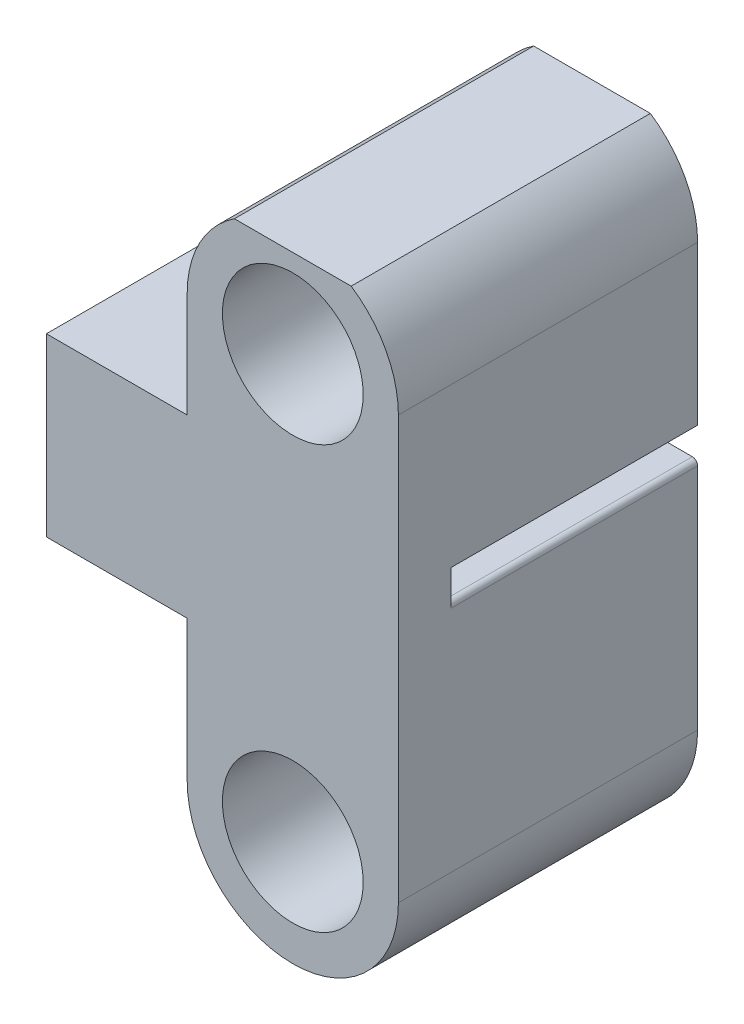
SolidWorks part; units mm, degrees
ref_plane "Front Plane" through (0, 0, 0) normal (0, 0, 1) x (1, 0, 0)
ref_plane "Top Plane" through (0, 0, 0) normal (0, 1, 0) x (1, 0, 0)
ref_plane "Right Plane" through (0, 0, 0) normal (1, 0, 0) x (0, 0, -1)
sketch "Sketch1" plane through (0, 0, 0) normal (0, 0, 1) x (1, 0, 0)
  line L0 (0, 0) -> (0, -12) construction
  line L1 (-3, 0) -> (-3, -12)
  line L2 (3, 0) -> (3, -12)
  arc A0 (3, 0) -> (-3, 0) centre (0, 0) ccw
  arc A1 (-3, -12) -> (3, -12) centre (0, -12) ccw
  circle A2 centre (0, 0) radius 2
  circle A3 centre (0, -12) radius 2
  dimension "D2" = 6
  dimension "D6" = 4
  dimension "D7" = 4
  dimension "D1" = 12
extrude "Boss-Extrude1" add sketch "Sketch1" along normal blind 8.5
sketch "Sketch2" plane through (3, 0, 0) normal (1, 0, 0) x (0, 0, -1)
  line L0 (-8.5, -6) -> (0, -6) construction
  line L1 (-8.5, -12) -> (-8.5, 0) construction
  line L2 (0, -12) -> (0, 0) construction
  line L3 (-4.25, 0) -> (-4.25, -12) construction
  line L4 (-8.5, 0) -> (0, 0) construction
  line L5 (-8.5, -12) -> (0, -12) construction
  circle A0 centre (-4.25, -8.5) radius 2
  dimension "D1" = 4
  dimension "D2" = 2.5
extrude "Cut-Extrude1" [suppressed] cut sketch "Sketch2" against normal through all
sketch "Sketch3" [suppressed] plane through (3, 0, 0) normal (1, 0, 0) x (0, 0, -1)
  line L1 (-0.6416, -8.5) -> (-2.4458, -5.375)
  line L2 (-2.4458, -5.375) -> (-6.0542, -5.375)
  line L3 (-6.0542, -5.375) -> (-7.8584, -8.5)
  line L4 (-7.8584, -8.5) -> (-6.0542, -11.625)
  line L5 (-6.0542, -11.625) -> (-2.4458, -11.625)
  line L6 (-2.4458, -11.625) -> (-0.6416, -8.5)
  line L7 (-1.8684, -4.375) -> (-6.6316, -4.375)
  line L8 (-6.6316, -4.375) -> (-9.0131, -8.5)
  line L9 (-9.0131, -8.5) -> (-6.6316, -12.625)
  line L10 (-6.6316, -12.625) -> (-1.8684, -12.625)
  line L11 (-1.8684, -12.625) -> (0.5131, -8.5)
  line L12 (0.5131, -8.5) -> (-1.8684, -4.375)
  circle A0 centre (-4.25, -8.5) radius 3.125 construction
  circle A1 centre (-4.25, -8.5) radius 4.125 construction
  dimension "D1" = 6.25
  dimension "D2" = 1
extrude "Boss-Extrude2" [suppressed] add sketch "Sketch3" along normal blind 2 and the other way blind 0.5
sketch "Sketch4" [suppressed] plane through (-3, 0, 0) normal (-1, 0, 0) x (0, 0, 1)
  line L0 (4.25, 0) -> (4.25, -6.5) construction
  line L1 (8.5, 0) -> (0, 0) construction
  line L3 (0.75, -2.75) -> (7.75, -2.75)
  line L4 (0.75, -2.75) -> (0.75, -5.75)
  line L5 (0.75, -5.75) -> (7.75, -5.75)
  line L6 (7.75, -2.75) -> (7.75, -5.75)
  line L7 (0.75, -2.75) -> (7.75, -5.75) construction
  line L8 (0.75, -5.75) -> (7.75, -2.75) construction
  circle A0 centre (4.25, -8.5) radius 2 construction
  point P7 (4.25, -4.25)
  dimension "D1" = 7
  dimension "D2" = 3
  dimension "D3" = 2.75
extrude "Cut-Extrude2" [suppressed] cut sketch "Sketch4" against normal through all
sketch "Sketch5" plane through (-3, 0, 0) normal (-1, 0, 0) x (0, 0, 1)
  line L0 (4.25, 0) -> (4.25, -12) construction
  line L1 (8.5, 0) -> (0, 0) construction
  line L2 (8.5, -12) -> (0, -12) construction
  line L3 (0, -6) -> (8.5, -6) construction
  line L4 (0, 0) -> (0, -12) construction
  line L5 (8.5, 0) -> (8.5, -12) construction
  line L7 (0, -15) -> (8.5, -15)
  line L8 (0, -15) -> (0, 3)
  line L9 (0, 3) -> (8.5, 3)
  line L10 (8.5, -15) -> (8.5, 3)
  line L11 (0, -15) -> (8.5, 3) construction
  line L12 (0, 3) -> (8.5, -15) construction
  point P12 (4.25, -6)
extrude "Cut-Extrude3" [suppressed] cut sketch "Sketch5" against normal through all flip side to cut
sketch "Sketch9" plane through (-3, 0, 0) normal (-1, 0, 0) x (0, 0, 1)
  line L0 (8.5, 0) -> (8.5, -12) construction
  line L1 (0, -3) -> (8.5, -3)
  line L2 (0, -3) -> (0, -8)
  line L3 (0, -8) -> (8.5, -8)
  line L4 (8.5, -3) -> (8.5, -8)
  line L5 (0, 0) -> (0, -12) construction
  line L6 (8.5, 0) -> (0, 0) construction
  dimension "D1" = 5
  dimension "D2" = 3
extrude "Boss-Extrude4" add sketch "Sketch9" along normal blind 4
sketch "Sketch6" plane through (3, 0, 0) normal (1, 0, 0) x (0, 0, -1)
  line L0 (0, -12) -> (0, 0) construction
  line L1 (0, -4.5) -> (-7, -4.5)
  line L2 (0, -4.5) -> (0, -6.1)
  line L3 (0, -6.1) -> (-7, -6.1)
  line L4 (-7, -4.5) -> (-7, -6.1)
  dimension "D1" = 1.6
  dimension "D2" = 4.5
  dimension "D3" = 7
extrude "Cut-Extrude5" cut sketch "Sketch6" against normal through all
sketch "Sketch7" plane through (0, 0, 7) normal (0, 0, -1) x (-1, 0, 0)
  line L0 (-3, -6.1) -> (-3, -5.5)
  line L1 (-3, -4.5) -> (-3, -6.1) construction
  line L2 (-2.85, -5.35) -> (-2.15, -5.35)
  line L3 (-2, -5.5) -> (-2, -6.1)
  line L4 (7, -6.1) -> (-3, -6.1) construction
  line L5 (-2, -6.1) -> (-3, -6.1)
  line L6 (-0.85, -5.35) -> (-0.15, -5.35)
  line L7 (0, -5.5) -> (0, -6.1)
  line L8 (0, -6.1) -> (-1, -6.1)
  line L9 (-1, -6.1) -> (-1, -5.5)
  line L10 (1.15, -5.35) -> (1.85, -5.35)
  line L11 (2, -5.5) -> (2, -6.1)
  line L12 (2, -6.1) -> (1, -6.1)
  line L13 (1, -6.1) -> (1, -5.5)
  line L14 (3.15, -5.35) -> (3.85, -5.35)
  line L15 (4, -5.5) -> (4, -6.1)
  line L16 (4, -6.1) -> (3, -6.1)
  line L17 (3, -6.1) -> (3, -5.5)
  line L18 (5.15, -5.35) -> (5.85, -5.35)
  line L19 (6, -5.5) -> (6, -6.1)
  line L20 (6, -6.1) -> (5, -6.1)
  line L21 (5, -6.1) -> (5, -5.5)
  arc A0 (-2.15, -5.35) -> (-2, -5.5) centre (-2.15, -5.5) cw
  arc A1 (-3, -5.5) -> (-2.85, -5.35) centre (-2.85, -5.5) cw
  arc A2 (-1, -5.5) -> (-0.85, -5.35) centre (-0.85, -5.5) cw
  arc A3 (-0.15, -5.35) -> (0, -5.5) centre (-0.15, -5.5) cw
  arc A4 (1, -5.5) -> (1.15, -5.35) centre (1.15, -5.5) cw
  arc A5 (1.85, -5.35) -> (2, -5.5) centre (1.85, -5.5) cw
  arc A6 (3, -5.5) -> (3.15, -5.35) centre (3.15, -5.5) cw
  arc A7 (3.85, -5.35) -> (4, -5.5) centre (3.85, -5.5) cw
  arc A8 (5, -5.5) -> (5.15, -5.35) centre (5.15, -5.5) cw
  arc A9 (5.85, -5.35) -> (6, -5.5) centre (5.85, -5.5) cw
  point P11 (-2, -5.35)
  point P14 (-3, -5.35)
  dimension "D3" = 0.15
  dimension "D1" = 1
  dimension "D2" = 0.75
  dimension "D4" = 5
extrude "Boss-Extrude3" add sketch "Sketch7" along normal through all
sketch "Sketch10" plane through (0, 0, 8.5) normal (0, 0, 1) x (1, 0, 0)
  line L1 (-2.5, 3.5) -> (2.5, 3.5)
  line L2 (-2.5, 3.5) -> (-2.5, 2.5)
  line L3 (-2.5, 2.5) -> (2.5, 2.5)
  line L4 (2.5, 3.5) -> (2.5, 2.5)
  line L5 (-2.5, 3.5) -> (2.5, 2.5) construction
  line L6 (-2.5, 2.5) -> (2.5, 3.5) construction
  arc A0 (3, 0) -> (-3, 0) centre (0, 0) ccw construction
  point P0 (0, 3)
  dimension "D1" = 1
  dimension "D2" = 5
extrude "Cut-Extrude6" cut sketch "Sketch10" against normal through all
equation "\"X-ROD-SPACING\"=45"
equation "\"Y-ROD-SPACING\"=75"
equation "\"Z-ROD-SPACING\"=17.5"
equation "\"Y-BED-OFFSET\"=2"
equation "\"Y-BED-ROD-INSET\"=3.5"
equation "\"Y-BED-SCREW-SPACING\"=209"
equation "\"Y-BED-SCREW-CUTOUT-SLOT-HEIGHT\"=2"
equation "\"T-SLOT-NUT-FILLET-RADIUS\"=0.5"
equation "\"T-SLOT-SCREW-SHAFT-RADIUS\"=1.55"
equation "\"T-SLOT-SCREW-SHAFT-CUTOUT-LENGTH\"=11.0"
equation "\"T-SLOT-NUT-DEPTH\"=3.5"
equation "\"T-SLOT-NUT-WIDTH\"=2.85"
equation "\"T-SLOT-NUT-END-DISTANCE\"=8"
equation "\"ACRYLIC-THICKNESS\"=10"
equation "\"ACRYLIC-THICKNESS2\"=4.5"
equation "\"ACRYLIC-TAB-CUTOUT-SIZE\"=\"ACRYLIC-THICKNESS\"+\"ACRYLIC-TAB-TOLERANCE\"*2"
equation "\"ACRYLIC-TAB-TOLERANCE\"=-.05"
equation "\"ACRYLIC-TAB-WIDTH\"=\"ACRYLIC-THICKNESS\""
equation "\"ACRYLIC-M3-HOLE\"=2.9"
equation "\"SMOOTHROD-CAP-SCREW-DISTANCE\"=20"
equation "\"FRAME-WIDTH-INNER\"=370"
equation "\"NEMA17-HOLE-SPACING\"=31"
equation "\"NEMA17-CENTRAL-CUTOUT\"=22.5"
equation "\"Z-BRACKET-REACH\"=55"
equation "\"Z-ROD-INSET\"=16"
equation "\"TOP-BRACKET-SPACING\"=40"
equation "\"SMOOTHROD-X-LENGTH\"=350"
equation "\"SMOOTHROD-Y-LENGTH\"=350"
equation "\"SMOOTHROD-Z-LENGTH\"=350"
equation "\"SMOOTHROD-TIGHTENING-HEADROOM\"=.25"
equation "\"LEADSCREW-Z-LENGTH\"=300"
equation "\"SCREW-LENGTH-FRAME\"=\"ACRYLIC-THICKNESS\" + 10"
equation "\"SCREW-LENGTH-MOTOR\"=\"ACRYLIC-THICKNESS\" + 5"
equation "\"SCREW-LENGTH-EXTRUDER\"=28"
equation "\"SCREW-HEAD-RADIUS\"=6"
equation "\"PRINTED-M3-HOLE\"=3.5"
equation "\"PRINTED-X-SMOOTHROD-DIAMETER\"=9.0"
equation "\"PRINTED-X-SMOOTHROD-CUTOUT\"=10"
equation "\"PRINTED-X-BASE-HEIGHT\"=10"
equation "\"PRINTED-LM8UU-CUTOUT-SIZE\"=15.5"
equation "\"PRINTED-LM8UU-CUTOUT-LENGTH\"=24.5"
equation "\"PRINTED-X-IDLER-HEIGHT\"=16"
equation "\"PRINTED-M3-NUT-AF\"=6.25"
equation "\"PSU-MOUNTING-WIDTH\"=95"
equation "\"PSU-MOUNTING-HEIGHT\"=177"
equation "\"Y-BELT-TO-ROD-DISTANCE\"=20"
equation "\"SPOOL-HOLDER-ROD-SPACING\"=150"
equation "\"ACRYLIC-X-CARRIAGE-WIDTH\"=55"
equation "\"ACRYLIC-X-CARRIAGE-HEIGHT\"=75"
equation "\"ACRYLIC-X-CARRIAGE-LM8UU-CUTOUT-WIDTH\"=24.25"
equation "\"ACRYLIC-X-CARRIAGE-LM8UU-CUTOUT-HEIGHT\"=11.0"
equation "\"ACRYLIC-X-CARRIAGE-SCREW-SPACING-X\"=15"
equation "\"ACRYLIC-X-CARRIAGE-SCREW-SPACING-Y\"=33"
equation "\"ACRYLIC-X-CARRIAGE-CENTER-TAB-SPACING\"=14"
equation "\"ACRYLIC-X-CARRIAGE-EXTRUDER-OFFSET\"=26"
equation "\"ACRYLIC-X-CARRIAGE-EXTRUDER-ANGLE\"=90"
equation "\"ACRYLIC-X-CARRIAGE-EXTRUDER-SHELF-DEPTH\"=\"ACRYLIC-X-CARRIAGE-EXTRUDER-OFFSET\" + 28"
equation "\"ACRYLIC-X-CARRIAGE-EXTRUDER-BRACE-SPACING\"=23"
equation "\"ACRYLIC-X-CARRIAGE-EXTRUDER-BRACE-TAB-OFFSET\"=20"
equation "\"ACRYLIC-X-CARRIAGE-EXTRUDER-BRACE-HEIGHT\"=35"
equation "\"ACRYLIC-X-CARRIAGE-EXTRUDER-BRACE-SCREW-SPACING\"=22"
equation "\"ACRYLIC-X-CARRIAGE-DUAL-WIDTH-MULTIPLIER\"=1.65"
equation "\"ACRYLIC-X-CARRIAGE-DUAL-HOTEND-SPACING\"=42"
equation "\"ACRYLIC-X-CARRIAGE-DUAL-WIDTH\"=75"
equation "\"ACRYLIC-X-CARRIAGE-DUAL-HOTEND-SEPARATION\"=36"
equation "\"ACRYLIC-X-CARRIAGE-DUAL-MOUNT-PLATE-DEPTH\"=75"
equation "\"ACRYLIC-X-CARRIAGE-DUAL-MOUNT-BRACE-WIDTH\"=33"
equation "\"ACRYLIC-X-CARRIAGE-DUAL-MOUNT-SCREW-WIDTH\"=40"
equation "\"BLOWER-FAN-WIDTH\"=15"
equation "\"D1@Sketch3\"=\"PRINTED-M3-NUT-AF\""
